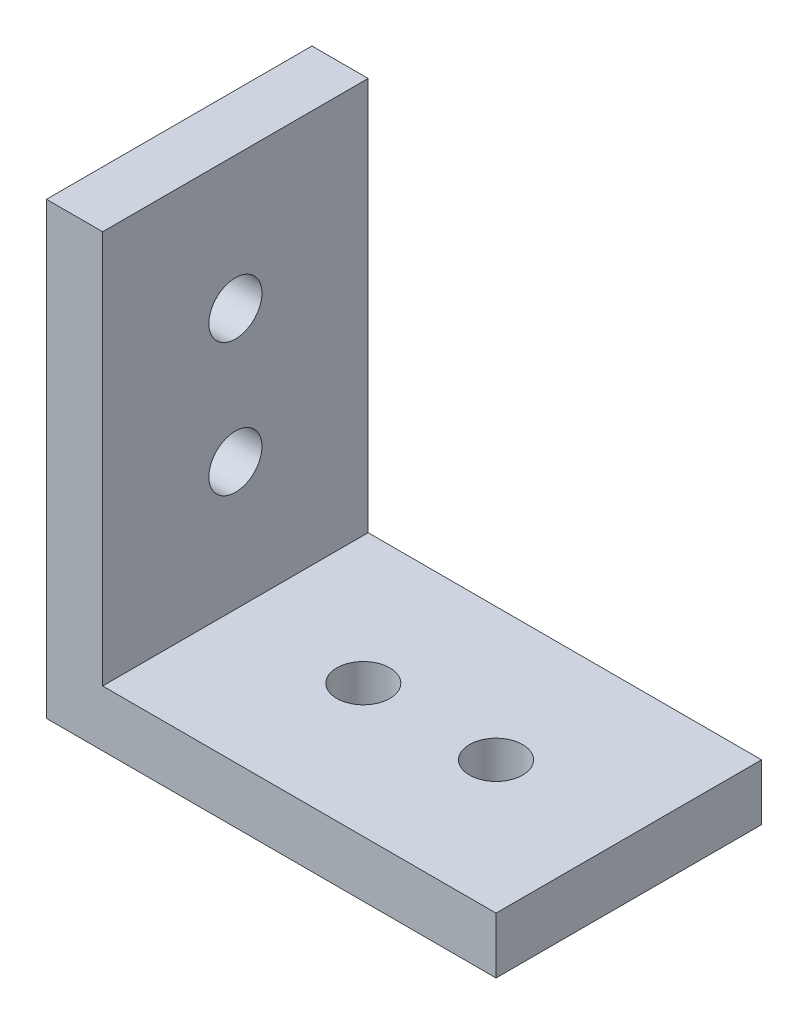
SolidWorks part; units mm, degrees
ref_plane "Front Plane" through (0, 0, 0) normal (0, 0, 1) x (1, 0, 0)
ref_plane "Top Plane" through (0, 0, 0) normal (0, 1, 0) x (1, 0, 0)
ref_plane "Right Plane" through (0, 0, 0) normal (1, 0, 0) x (0, 0, -1)
sketch "Sketch1" plane through (0, 0, 0) normal (1, 0, 0) x (0, 0, -1)
  line L1 (0, 0) -> (15, 0)
  line L2 (0, 0) -> (0, 25.4)
  line L3 (0, 25.4) -> (15, 25.4)
  line L4 (15, 0) -> (15, 25.4)
  dimension "D1" = 25.4
  dimension "D2" = 15
extrude "Boss-Extrude1" add sketch "Sketch1" along normal blind 3.175
sketch "Sketch2" plane through (3.175, 0, 0) normal (1, 0, 0) x (0, 0, -1)
  line L0 (15, 0) -> (15, 25.4) construction
  line L1 (0, 0) -> (15, 0)
  line L2 (0, 0) -> (0, 3.175)
  line L3 (0, 3.175) -> (15, 3.175)
  line L4 (15, 0) -> (15, 3.175)
  dimension "D1" = 3.175
extrude "Boss-Extrude2" add sketch "Sketch2" along normal blind 22.225
sketch "Sketch3" plane through (0, 0, 0) normal (0, -1, 0) x (1, 0, 0)
  circle A2 centre (10.4, -7.5) radius 1.5
  circle A3 centre (17.9, -7.5) radius 1.5
sketch "Sketch4" plane through (3.175, 0, 0) normal (1, 0, 0) x (0, 0, -1)
  line L0 (7.5, 25.4) -> (7.5, 10.4)
  line L1 (15, 25.4) -> (0, 25.4) construction
  circle A0 centre (7.5, 17.9) radius 1.5
  circle A1 centre (7.5, 10.4) radius 1.5
  dimension "D1" = 15
extrude "Cut-Extrude3" cut sketch "Sketch4" against normal through all contours A0 | A1
extrude "Cut-Extrude4" cut sketch "Sketch3" against normal through all
